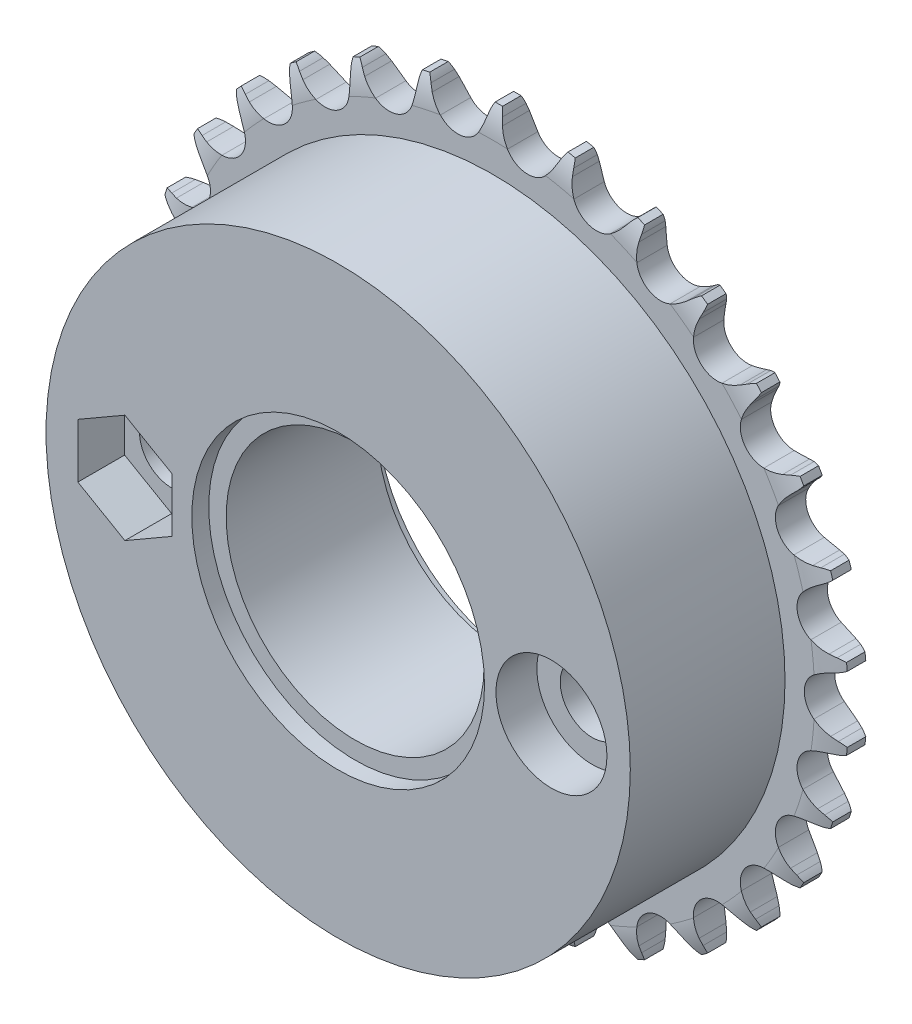
SolidWorks part; units mm, degrees
ref_plane "Front Plane" through (0, 0, 0) normal (0, 0, 1) x (1, 0, 0)
ref_plane "Top Plane" through (0, 0, 0) normal (0, 1, 0) x (1, 0, 0)
ref_plane "Right Plane" through (0, 0, 0) normal (1, 0, 0) x (0, 0, -1)
sketch "Sketch0" plane through (0, 0, 0) normal (0, 0, 1) x (1, 0, 0)
  line L0 (3, -28.5431) -> (0, 0) construction
  line L1 (0, 0) -> (8.8689, -27.2956) construction
  line L2 (0, 0) -> (-3, -28.5431) construction
  line L3 (3, -28.5431) -> (8.8689, -27.2956) construction
  line L4 (3, -28.5431) -> (-3, -28.5431) construction
  line L5 (5.5888, -28.8423) -> (5.3413, -28.3538)
  line L6 (3, -28.5431) -> (0, -28.8584) construction
  line L7 (0.53, -29.374) -> (0.6705, -28.8447)
  line L8 (0, -28.5431) -> (0, -30.3431) construction
  line L9 (4.4979, -27.1463) -> (0.6597, -30.7255) construction
  line L10 (0, 0) -> (0, -28.5431) construction
  line L11 (5.3413, -28.3538) -> (0.6597, -30.7255) construction
  line L12 (0, -30.3431) -> (0, -30.4737) construction
  line L13 (8.4776, -27.3788) -> (5.5888, -28.8423) construction
  circle A0 centre (0, 0) radius 30.3431 construction
  circle A1 centre (0, 0) radius 28.7003 construction
  arc A2 (-2.8938, -31.7682) -> (9.4355, -30.4723) centre (0, 0) ccw
  circle A3 centre (0, 0) radius 30.4737 construction
  circle A4 centre (3, -28.5431) radius 2 construction
  arc A7 (4.4979, -27.1463) -> (1.2444, -27.4882) centre (3, -28.5431) ccw
  circle A8 centre (3, -28.5431) radius 2.0481 construction
  arc A9 (5.5888, -28.8423) -> (9.4355, -30.4723) centre (8.4776, -27.3788) ccw
  arc A10 (5.3413, -28.3538) -> (4.4979, -27.1463) centre (0.6597, -30.7255) ccw
  arc A11 (0.53, -29.374) -> (-2.8938, -31.7682) centre (-2.6, -28.5431) cw
  arc A12 (0.6705, -28.8447) -> (1.2444, -27.4882) centre (5.7429, -30.1912) cw
  dimension "D1" = 2.0481
  dimension "R" = 2.0481
sketch "Sketch1" plane through (0, 0, 0) normal (1, 0, 0) x (0, 0, -1)
  line L0 (1.3, 0) -> (-1.3, 0)
  line L1 (-1.3, 0) -> (-1.3, 27.5306)
  line L2 (-1.3, 28.7003) -> (0, 28.7003) construction
  line L3 (-0.6, 30.3431) -> (0.6, 30.3431)
  line L5 (1.3, 27.5306) -> (1.3, 0)
  line L7 (0, 30.3431) -> (0, 0) construction
  line L8 (-1.3, 27.5306) -> (1.3, 27.5306) construction
  line L9 (0, 30.3431) -> (0, -30.3431) construction
  line L10 (-1.3, 27.5306) -> (-1.3, 30.3431) construction
  line L11 (-1.3, 30.3431) -> (-0.6, 30.3431) construction
  line L12 (0.6, 30.3431) -> (1.3, 30.3431) construction
  line L13 (1.3, 30.3431) -> (1.3, 27.5306) construction
  line L14 (0, 0) -> (-6.4008, 0) construction
  line L15 (-1.3, 28.7003) -> (-1.3, 24.6003) construction
  line L22 (1.3, 0) -> (-13.7, 0) construction
  line L24 (-1.3, 0) -> (-1.3, 24.6003) construction
  arc A0 (-0.6, 30.3431) -> (-1.3, 27.5306) centre (4.7, 27.5306) ccw
  arc A1 (0.6, 30.3431) -> (1.3, 27.5306) centre (-4.7, 27.5306) cw
  dimension "R" = 6
revolve "Revolve1" add sketch "Sketch1" angle 360 mid plane about L0
extrude "Cut-Extrude1" cut sketch "Sketch0" against normal through all and the other way through all
pattern_circular "CirPattern1" count 30 over 360 about axis through (0, 0, -1.3) along (0, 0, -1) of "Cut-Extrude1"
sketch "Sketch2" plane through (0, 0, 0) normal (0, 0, 1) x (1, 0, 0)
  circle A0 centre (0, 0) radius 4 construction
  circle A1 centre (0, 0) radius 15
  circle A2 centre (0, 0) radius 29.95 construction
  dimension "Bore" = 8
  dimension "Hub Dia." = 30
  dimension "OD" = 59.9
extrude "Boss-Extrude1" add sketch "Sketch2" along normal up to vertex (13.7 mm away) from surface up to point (0, 0, 13.7) starting at face at (0, 0, 1.3)
sketch "Sketch3" plane through (0, 0, 0) normal (0, 0, 1) x (1, 0, 0)
  circle A0 centre (0, 0) radius 4 construction
  circle A1 centre (0, 0) radius 4
extrude "Cut-Extrude2" cut sketch "Sketch3" along normal through all and the other way through all
sketch "Sketch4" plane through (0, 0, 0) normal (1, 0, 0) x (0, 0, -1)
  line L0 (-13.7, 15) -> (-13.7, 14.5)
  line L1 (-1.3, 30.3431) -> (-3.25, 30.3431)
  line L2 (-1.3, 30.3431) -> (-1.3, 24.6003)
  line L3 (-1.3, 24.6003) -> (-3.25, 24.6003)
  line L4 (-3.25, 30.3431) -> (-3.25, 24.6003)
  line L9 (-13.7, 14.5) -> (-13.2, 15)
  line L10 (-13.2, 15) -> (-13.7, 15)
  dimension "C" = 0.5
  dimension "D3" = 1.95
revolve "Cut-Revolve1" cut sketch "Sketch4" angle 360 mid plane about L22
sketch "Sketch5" plane through (0, 0, 0) normal (0, 0, 1) x (1, 0, 0)
  circle A0 centre (0, 0) radius 29.95 construction
  circle A1 centre (0, 0) radius 29.95
extrude "Cut-Extrude3" cut sketch "Sketch5" against normal through all and the other way through all flip side to cut
sketch "Sketch6" plane through (0, 0, -1.3) normal (0, 0, -1) x (-1, 0, 0)
  circle A0 centre (0, 0) radius 25
  dimension "D1" = 50
sketch "Sketch7" plane through (0, 0, 1.3) normal (0, 0, 1) x (1, 0, 0)
  circle A0 centre (0, 0) radius 25
  dimension "D1" = 50
extrude "Boss-Extrude3" add sketch "Sketch7" along normal blind 13.24
sketch "Sketch8" plane through (0, 0, 0) normal (0, 0, 1) x (1, 0, 0)
  circle A0 centre (0, 0) radius 11.0375
  dimension "D1" = 22.075
extrude "Cut-Extrude4" cut sketch "Sketch8" against normal through all both and the other way through all
sketch "Sketch9" plane through (0, 0, 14.54) normal (0, 0, 1) x (1, 0, 0)
  circle A0 centre (0, 0) radius 12.525
  dimension "D1" = 25.05
extrude "Cut-Extrude5" cut sketch "Sketch9" against normal blind 1.45
sketch "Sketch11" plane through (0, 0, 0) normal (0, 0, 1) x (1, 0, 0)
  line L0 (-42.3042, 0) -> (41.8036, 0) construction
  line L1 (0, 35.6238) -> (0, -32.3172) construction
  circle A0 centre (18.25, 0) radius 2.75
  circle A1 centre (-18.25, 0) radius 2.75
  dimension "D1" = 5.5
  dimension "D2" = 18.25
extrude "Cut-Extrude7" cut sketch "Sketch11" against normal through all both and the other way through all
sketch "Sketch12" plane through (0, 0, 14.54) normal (0, 0, 1) x (1, 0, 0)
  circle A0 centre (18.25, 0) radius 4.75
  dimension "D1" = 9.5
extrude "Cut-Extrude8" cut sketch "Sketch12" against normal blind 3.5
sketch "Sketch13" plane through (0, 0, 14.54) normal (0, 0, 1) x (1, 0, 0)
  line L1 (-18.25, 4.6477) -> (-22.275, 2.3238)
  line L2 (-22.275, 2.3238) -> (-22.275, -2.3238)
  line L3 (-22.275, -2.3238) -> (-18.25, -4.6477)
  line L4 (-18.25, -4.6477) -> (-14.225, -2.3238)
  line L5 (-14.225, -2.3238) -> (-14.225, 2.3238)
  line L6 (-14.225, 2.3238) -> (-18.25, 4.6477)
  circle A0 centre (-18.25, 0) radius 4.025 construction
  dimension "D1" = 8.05
extrude "Cut-Extrude9" cut sketch "Sketch13" against normal blind 4
sketch "Sketch16" plane through (0, 0, -1.3) normal (0, 0, -1) x (-1, 0, 0)
  circle A0 centre (0, 0) radius 12.525
  dimension "D1" = 25.05
extrude "Cut-Extrude12" cut sketch "Sketch16" against normal blind 1.45
sketch "Sketch17" plane through (0, 0, -1.3) normal (0, 0, -1) x (-1, 0, 0)
  circle A0 centre (18.25, 0) radius 4.75
  dimension "D1" = 9.5
extrude "Cut-Extrude13" cut sketch "Sketch17" against normal blind 3.5
sketch "Sketch18" plane through (0, 0, -1.3) normal (0, 0, -1) x (-1, 0, 0)
  line L1 (-18.25, 4.6477) -> (-22.275, 2.3238)
  line L2 (-22.275, 2.3238) -> (-22.275, -2.3238)
  line L3 (-22.275, -2.3238) -> (-18.25, -4.6477)
  line L4 (-18.25, -4.6477) -> (-14.225, -2.3238)
  line L5 (-14.225, -2.3238) -> (-14.225, 2.3238)
  line L6 (-14.225, 2.3238) -> (-18.25, 4.6477)
  circle A0 centre (-18.25, 0) radius 4.025 construction
  dimension "D1" = 8.05
extrude "Cut-Extrude14" cut sketch "Sketch18" against normal blind 4
equation "\"360/N@Sketch0\" = 360/\"Teeth@CirPattern1\""
equation "\"Ds@Sketch0\" = 1.005 * \"Dr@Sketch0\" + ( 0.003 * 25.4 ) "
equation "\"R@Sketch0\" = 1/2 * \"Ds@Sketch0\""
equation "\"A@Sketch0\" = 35 +  ( 60 / \"Teeth@CirPattern1\" ) "
equation "\"B@Sketch0\" = 18 -  ( 56 / \"Teeth@CirPattern1\" )"
equation "\"ac@Sketch0\" = 0.8 * \"Dr@Sketch0\""
equation "\"ab@Sketch0\" = 1.4 * \"Dr@Sketch0\""
equation "\"J@Sketch0\" = 0.3 * \"Pitch@Sketch0\""
equation "\"D3@Sketch4\" = \"t@Sketch1\" * 3 / 4"
